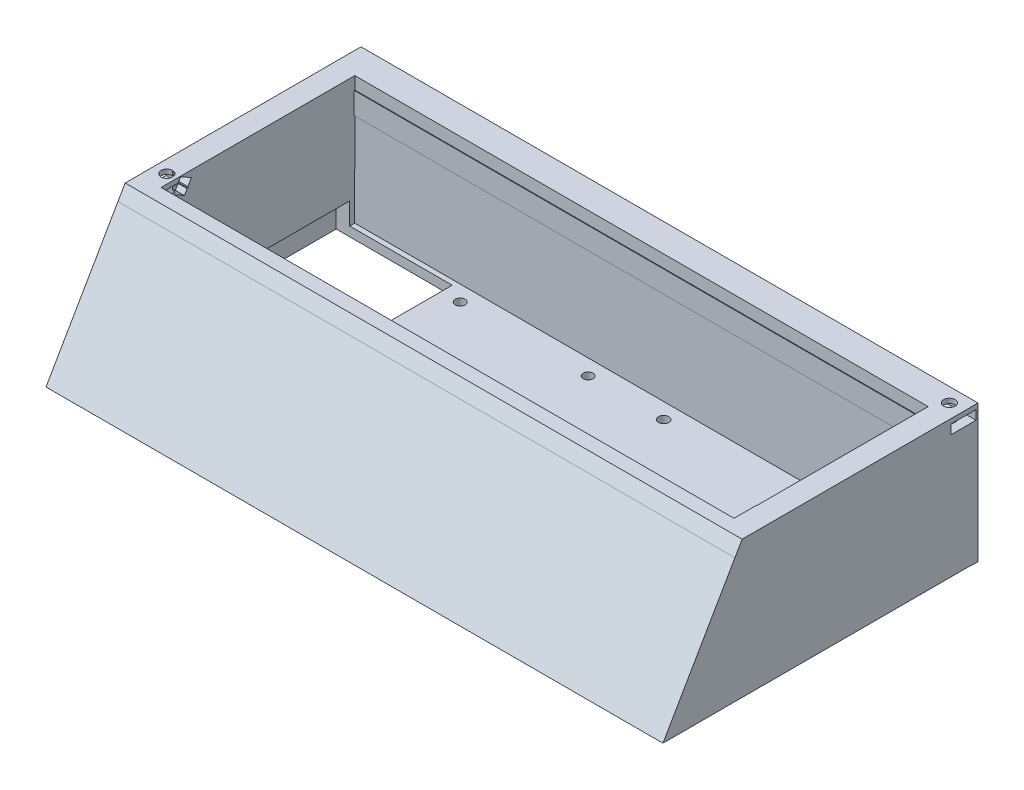
SolidWorks part; units mm, degrees
ref_plane "Alzado" through (0, 0, 0) normal (0, 0, 1) x (1, 0, 0)
ref_plane "Planta" through (0, 0, 0) normal (0, 1, 0) x (1, 0, 0)
ref_plane "Vista lateral" through (0, 0, 0) normal (1, 0, 0) x (0, 0, -1)
sketch "Sketch1" plane through (0, 0, 0) normal (1, 0, 0) x (0, 0, -1)
  line L0 (22.1085, 0) -> (32.4418, 17.8992)
  line L3 (-73.8644, -51.971) -> (121.1356, -51.9647) construction
  line L4 (22.1085, 0) -> (121.18, 0)
  line L5 (121.18, 0) -> (121.2142, 40)
  line L6 (45.2007, 40) -> (121.2142, 40)
  line L7 (32.4418, 17.8992) -> (45.2007, 40)
  line L8 (121.1416, -44.9647) -> (121.18, 0) construction
  dimension "D1" = 120
  dimension "D2" = 40
  dimension "D3" = 120
  dimension "D4" = 76.0135
extrude "Boss-Extrude1" add sketch "Sketch1" along normal blind 198
shell "Shell1" thickness 7 removed face at (99, 0, -71.6442)
sketch "Sketch2" plane through (0, 0, 0) normal (-1, 0, 0) x (0, 0, 1)
  line L0 (-30.1912, 0) -> (-32.9749, 0)
  line L1 (-32.9749, 0) -> (-52.026, 33)
  line L2 (73.8644, -51.971) -> (-121.1356, -51.9647) construction
  line L3 (-52.026, 33) -> (-49.2423, 33)
  line L4 (-49.2423, 33) -> (-30.1912, 0)
  dimension "D1" = 120
extrude "Boss-Extrude2" add sketch "Sketch2" against normal blind 191
ref_plane "Plane1" through (99, 0, 0) normal (1, 0, 0) x (0, 0, -1)
sketch "Sketch6" plane through (0, -0.1036, -121.1799) normal (0, -0.0009, -1) x (-1, 0, 0)
  line L1 (-198, 40.1036) -> (0, 40.1036)
  line L2 (-198, 40.1036) -> (-198, 0)
  line L3 (-198, 0) -> (0, 0)
  line L4 (0, 40.1036) -> (0, 0)
extrude "Boss-Extrude4" add sketch "Sketch6" along normal blind 2
sketch "Sketch7" plane through (0, 0, 0) normal (-1, 0, 0) x (0, 0, 1)
  line L1 (-123.1877, 9.047) -> (-35.2379, 9.047)
  line L2 (-123.1877, 9.047) -> (-123.1877, 12.047)
  line L3 (-123.1877, 12.047) -> (-35.2379, 12.047)
  line L4 (-35.2379, 9.047) -> (-35.2379, 12.047)
  dimension "D1" = 3
  dimension "D2" = 87.9498
  dimension "D3" = 3
ref_plane "Plane3" through (0, -0.0976, -114.1799) normal (0, 0.0009, 1) x (1, 0, 0)
ref_plane "Plane4" through (0, -14.278, -24.7321) normal (0, -0.5, -0.866) x (-1, 0, 0)
ref_plane "Plane5" through (7, 0, 0) normal (1, 0, 0) x (0, 0, -1)
ref_plane "Plane6" through (191, 0, 0) normal (-1, 0, 0) x (0, 0, 1)
sketch "Sketch8" plane through (198, 0, 0) normal (1, 0, 0) x (0, 0, -1)
  line L0 (123.2142, 39.9983) -> (123.2142, 52.0483)
  line L1 (123.2142, 39.9983) -> (45.2007, 40)
  line L2 (45.2007, 40) -> (52.1572, 52.0483)
  line L3 (123.2142, 52.0483) -> (52.1572, 52.0483)
  dimension "D1" = 12.05
  dimension "D2" = 78.0135
extrude "Boss-Extrude6" add sketch "Sketch8" against normal blind 198
sketch "Sketch9" plane through (0, 40.001, -0.0009) normal (0, -1, 0) x (-1, 0, 0)
  line L0 (0, 52.156) -> (-198, 52.156) construction
  line L1 (-7, 114.2131) -> (-191, 114.2131)
  line L2 (-7, 114.2131) -> (-7, 59.156)
  line L3 (-7, 59.156) -> (-191, 59.156)
  line L4 (-191, 114.2131) -> (-191, 59.156)
  line L5 (0, 123.2131) -> (0, 52.156) construction
  line L6 (0, 123.2131) -> (-198, 123.2131) construction
  line L7 (-198, 123.2131) -> (-198, 52.156) construction
  dimension "D1" = 7
  dimension "D2" = 7
  dimension "D3" = 9
  dimension "D4" = 7
extrude "Cut-Extrude1" cut sketch "Sketch9" against normal blind 4
sketch "Sketch10" plane through (0, -14.278, -24.7321) normal (0, -0.5, -0.866) x (-1, 0, 0)
  line L1 (-195.105, 67.1286) -> (-4.105, 67.1286)
  line L2 (-195.105, 67.1286) -> (-195.105, 62.6734)
  line L3 (-195.105, 62.6734) -> (-4.105, 62.6734)
  line L4 (-4.105, 67.1286) -> (-4.105, 62.6734)
  dimension "D1" = 191
  dimension "D2" = 191
extrude "Cut-Extrude2" cut sketch "Sketch10" along normal blind 4
ref_plane "Plane7" through (0, 44.001, -0.001) normal (0, -1, 0) x (-1, 0, 0)
split "Split4" trim tools "Plane7" bodies to split 114 resulting bodies 121
sketch "Sketch11" plane through (0, 44.001, -0.001) normal (0, 1, 0) x (1, 0, 0)
  circle A0 centre (4.1226, 56.7722) radius 1.8459
  circle A1 centre (193.3782, 118.6596) radius 1.8365
extrude "Cut-Extrude3" cut sketch "Sketch11" against normal blind 10
sketch "Sketch13" plane through (0, 0, 0) normal (-1, 0, 0) x (0, 0, 1)
  line L0 (-47.5102, 43.9999) -> (-123.2142, 43.9983) construction
  line L1 (-60.6515, 42.4996) -> (-52.6515, 42.4998)
  line L2 (-60.6515, 42.4996) -> (-60.6515, 39.4996)
  line L3 (-60.6515, 39.4996) -> (-52.6515, 39.4998)
  line L4 (-52.6515, 42.4998) -> (-52.6515, 39.4998)
  dimension "D1" = 8
  dimension "D2" = 3
  dimension "D3" = 3
  dimension "D4" = 1.5
extrude "Cut-Extrude4" cut sketch "Sketch13" against normal blind 10
sketch "Sketch15" plane through (198, 0, 0) normal (1, 0, 0) x (0, 0, -1)
  line L1 (122.5785, 42.4983) -> (114.5785, 42.4985)
  line L2 (122.5785, 42.4983) -> (122.5785, 39.5153)
  line L3 (122.5785, 39.5153) -> (114.5785, 39.5153)
  line L4 (114.5785, 42.4985) -> (114.5785, 39.5153)
  line L6 (47.5102, 43.9999) -> (123.2142, 43.9983) construction
  dimension "D1" = 1.5
  dimension "D2" = 8
extrude "Cut-Extrude6" cut sketch "Sketch15" against normal blind 10
sketch "Sketch16" plane through (0, 33, 0) normal (0, -1, 0) x (-1, 0, 0)
  line L1 (-7, 52.026) -> (-190.8842, 52.026)
  line L2 (-7, 52.026) -> (-7, 114.0066)
  line L3 (-7, 114.0066) -> (-190.8842, 114.0066)
  line L4 (-190.8842, 52.026) -> (-190.8842, 114.0066)
extrude "Cut-Extrude7" cut sketch "Sketch16" against normal blind 15
sketch "Sketch17" plane through (191, 0, 0) normal (-1, 0, 0) x (0, 0, 1)
  line L1 (-118.3902, 0) -> (-28.102, 0)
  line L2 (-118.3902, 0) -> (-118.3902, 3)
  line L3 (-118.3902, 3) -> (-28.102, 3)
  line L4 (-28.102, 0) -> (-28.102, 3)
  dimension "D1" = 90.2882
  dimension "D2" = 90.2882
  dimension "D3" = 3
  dimension "D4" = 3
extrude "Boss-Extrude7" add sketch "Sketch17" along normal blind 184
sketch "Sketch18" plane through (0, 0, 0) normal (0, -1, 0) x (1, 0, 0)
  circle A0 centre (186.292, -44.8599) radius 1.585
  circle A1 centre (11.7059, -44.8771) radius 1.6321
  circle A2 centre (11.7059, -44.8771) radius 1.585 construction
  dimension "D1" = 3.17
  dimension "D2" = 0
extrude "Cut-Extrude8" cut sketch "Sketch18" against normal blind 10
sketch "Sketch19" plane through (0, 0, 0) normal (0, -1, 0) x (1, 0, 0)
  line L1 (39.8872, -50.3796) -> (2.6595, -50.3796)
  line L2 (39.8872, -50.3796) -> (39.8872, -112.5753)
  line L3 (39.8872, -112.5753) -> (2.6595, -112.5753)
  line L4 (2.6595, -50.3796) -> (2.6595, -112.5753)
extrude "Cut-Extrude9" cut sketch "Sketch19" against normal blind 10
mirror "Mirror1" about plane through (99, 0, 0) normal (1, 0, 0) of "Cut-Extrude9"
sketch "Sketch20" plane through (0, 0, 0) normal (0, -1, 0) x (1, 0, 0)
  line L1 (177.525, -53.8323) -> (19.3377, -53.8323)
  line L2 (177.525, -53.8323) -> (177.525, -33.3446)
  line L3 (177.525, -33.3446) -> (19.3377, -33.3446)
  line L4 (19.3377, -53.8323) -> (19.3377, -33.3446)
  point P4 (0, 0)
  point P5 (0, 0)
  point P6 (19.3377, -50.3796)
  point P7 (177.525, -50.3794)
  point P8 (177.525, -52.2167)
  point P9 (177.525, -53.8323)
  point P10 (19.3377, -53.8323)
extrude "Cut-Extrude12" cut sketch "Sketch20" against normal blind 3
sketch "Sketch21" plane through (0, 3, 0) normal (0, 1, 0) x (1, 0, 0)
  line L1 (39.8872, 74.1) -> (158.1128, 74.1)
  line L2 (39.8872, 74.1) -> (39.8872, 53.8323)
  line L3 (39.8872, 53.8323) -> (158.1128, 53.8323)
  line L4 (158.1128, 74.1) -> (158.1128, 53.8323)
extrude "Cut-Extrude13" cut sketch "Sketch21" against normal blind 3
sketch "Sketch22" plane through (0, 0, 0) normal (0, -1, 0) x (-1, 0, 0)
  circle A0 centre (-152.0937, 109.1748) radius 1.585
  point P4 (0, 0)
  dimension "D1" = 3.17
extrude "Cut-Extrude14" cut sketch "Sketch22" against normal blind 17
sketch "Sketch23" plane through (0, 0, 0) normal (0, -1, 0) x (1, 0, 0)
  circle A0 centre (111.1584, -109.1729) radius 1.6451
  circle A1 centre (86.9191, -109.1729) radius 1.5695
  circle A2 centre (45.8637, -109.1729) radius 1.585
  point P6 (45.8637, -109.1729)
  dimension "D1" = 3.17
extrude "Cut-Extrude15" cut sketch "Sketch23" against normal blind 17
